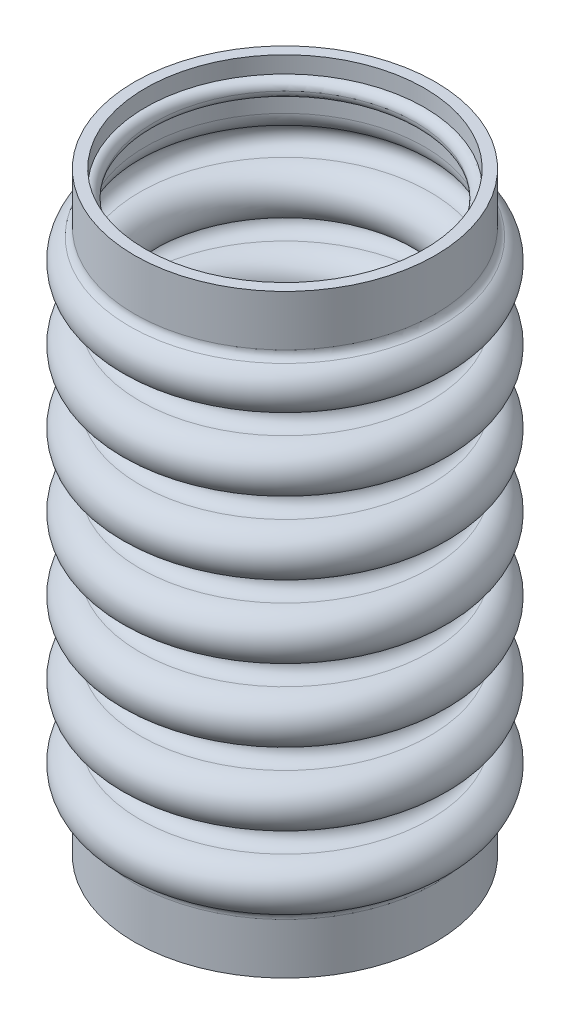
SolidWorks part; units mm, degrees
ref_plane "Front Plane" through (0, 0, 0) normal (0, 0, 1) x (1, 0, 0)
ref_plane "Top Plane" through (0, 0, 0) normal (0, 1, 0) x (1, 0, 0)
ref_plane "Right Plane" through (0, 0, 0) normal (1, 0, 0) x (0, 0, -1)
sketch "Sketch1" plane through (0, 0, 0) normal (0, 0, 1) x (1, 0, 0)
  line L0 (-46.087, 0) -> (53.9921, 0) construction
  line L1 (0, 81.831) -> (0, -42.6877) construction
  line L2 (-20, 0) -> (-20, 8.4666) construction
  line L3 (-20, 5) -> (0, 5) construction
  line L4 (0, 80) -> (-20, 80) construction
  line L5 (-20, 85) -> (-20, 76.5349) construction
  line L6 (-20.75, 85) -> (-20.75, 76.5349)
  line L7 (-20.75, 0) -> (-20.75, 8.4666)
  line L8 (-19.25, 85) -> (-19.25, 76.5349)
  line L9 (-19.25, 0) -> (-19.25, 8.4666)
  line L10 (-20.75, 85) -> (-19.25, 85)
  line L11 (-20.75, 0) -> (-19.25, 0)
  arc A0 (-21.1132, 10.2592) -> (-20.0029, 15) centre (-20.0046, 12.5) cw construction
  arc A1 (-20.0029, 15) -> (-20.0044, 20) centre (-20.0012, 17.5) ccw construction
  arc A2 (-20.0044, 20) -> (-20.0029, 25) centre (-20.0046, 22.5) cw construction
  arc A3 (-20.0029, 25) -> (-20.0044, 30) centre (-20.0012, 27.5) ccw construction
  arc A4 (-20.0044, 30) -> (-20.0029, 35) centre (-20.0046, 32.5) cw construction
  arc A5 (-20.0029, 35) -> (-20.0044, 40) centre (-20.0012, 37.5) ccw construction
  arc A6 (-20.0044, 40) -> (-20.0029, 45) centre (-20.0046, 42.5) cw construction
  arc A7 (-20.0029, 45) -> (-20.0044, 50) centre (-20.0012, 47.5) ccw construction
  arc A8 (-20.0044, 50) -> (-20.0029, 55) centre (-20.0046, 52.5) cw construction
  arc A9 (-20.0029, 55) -> (-20.0044, 60) centre (-20.0012, 57.5) ccw construction
  arc A10 (-20.0044, 60) -> (-20.0029, 65) centre (-20.0046, 62.5) cw construction
  arc A11 (-20.0029, 65) -> (-20.0044, 70) centre (-20.0012, 67.5) ccw construction
  arc A12 (-20.0044, 70) -> (-21.1145, 74.7416) centre (-20.0076, 72.5) cw construction
  arc A13 (-20, 76.5349) -> (-21.1145, 74.7416) centre (-22, 76.5349) cw construction
  arc A14 (-21.1132, 10.2592) -> (-20, 8.4666) centre (-22, 8.4666) cw construction
  arc A15 (-20.75, 76.5349) -> (-21.4465, 75.4141) centre (-22, 76.5349) cw
  arc A16 (-20.0034, 69.25) -> (-21.4465, 75.4141) centre (-20.0076, 72.5) cw
  arc A17 (-20.0024, 65.75) -> (-20.0034, 69.25) centre (-20.0012, 67.5) ccw
  arc A18 (-20.0039, 59.25) -> (-20.0024, 65.75) centre (-20.0046, 62.5) cw
  arc A19 (-20.0024, 55.75) -> (-20.0039, 59.25) centre (-20.0012, 57.5) ccw
  arc A20 (-20.0039, 49.25) -> (-20.0024, 55.75) centre (-20.0046, 52.5) cw
  arc A21 (-20.0024, 45.75) -> (-20.0039, 49.25) centre (-20.0012, 47.5) ccw
  arc A22 (-20.0039, 39.25) -> (-20.0024, 45.75) centre (-20.0046, 42.5) cw
  arc A23 (-20.0024, 35.75) -> (-20.0039, 39.25) centre (-20.0012, 37.5) ccw
  arc A24 (-20.0039, 29.25) -> (-20.0024, 35.75) centre (-20.0046, 32.5) cw
  arc A25 (-20.0024, 25.75) -> (-20.0039, 29.25) centre (-20.0012, 27.5) ccw
  arc A26 (-20.0039, 19.25) -> (-20.0024, 25.75) centre (-20.0046, 22.5) cw
  arc A27 (-20.0024, 15.75) -> (-20.0039, 19.25) centre (-20.0012, 17.5) ccw
  arc A28 (-21.4457, 9.587) -> (-20.0024, 15.75) centre (-20.0046, 12.5) cw
  arc A29 (-21.4457, 9.587) -> (-20.75, 8.4666) centre (-22, 8.4666) cw
  arc A30 (-19.25, 76.5349) -> (-20.7824, 74.0691) centre (-22, 76.5349) cw
  arc A31 (-20.0053, 70.75) -> (-20.7824, 74.0691) centre (-20.0076, 72.5) cw
  arc A32 (-20.0034, 64.25) -> (-20.0053, 70.75) centre (-20.0012, 67.5) ccw
  arc A33 (-20.0049, 60.75) -> (-20.0034, 64.25) centre (-20.0046, 62.5) cw
  arc A34 (-20.0034, 54.25) -> (-20.0049, 60.75) centre (-20.0012, 57.5) ccw
  arc A35 (-20.0049, 50.75) -> (-20.0034, 54.25) centre (-20.0046, 52.5) cw
  arc A36 (-20.0034, 44.25) -> (-20.0049, 50.75) centre (-20.0012, 47.5) ccw
  arc A37 (-20.0049, 40.75) -> (-20.0034, 44.25) centre (-20.0046, 42.5) cw
  arc A38 (-20.0034, 34.25) -> (-20.0049, 40.75) centre (-20.0012, 37.5) ccw
  arc A39 (-20.0049, 30.75) -> (-20.0034, 34.25) centre (-20.0046, 32.5) cw
  arc A40 (-20.0034, 24.25) -> (-20.0049, 30.75) centre (-20.0012, 27.5) ccw
  arc A41 (-20.0049, 20.75) -> (-20.0034, 24.25) centre (-20.0046, 22.5) cw
  arc A42 (-20.0034, 14.25) -> (-20.0049, 20.75) centre (-20.0012, 17.5) ccw
  arc A43 (-20.7806, 10.9314) -> (-20.0034, 14.25) centre (-20.0046, 12.5) cw
  arc A44 (-20.7806, 10.9314) -> (-19.25, 8.4666) centre (-22, 8.4666) cw
  point P45 (-20, 75)
  point P48 (-20, 10)
  point P49 (-20, 75)
  dimension "D3" = 2.5
  dimension "D4" = 2.5
  dimension "D12" = 2
  dimension "D13" = 2
  dimension "D1" = 20
  dimension "D2" = 10
  dimension "D5" = 5
  dimension "D6" = 75
  dimension "D7" = 10
  dimension "D8" = 5
  dimension "D10" = 20
  dimension "D11" = 5
  dimension "D14" = 0.75
  dimension "D15" = 0.75
  dimension "D9" = 6
revolve "Revolve1" add sketch "Sketch1" angle 360 about L1
sketch "Sketch3" plane through (0, 0, 0) normal (1, 0, 0) x (0, 0, -1)
  line L0 (20.75, 76.5349) -> (20.75, 85) construction
  line L1 (-20.75, 85) -> (20.75, 85)
  line L2 (-20.75, 85) -> (-20.75, 83.5349)
  line L3 (-20.75, 83.5349) -> (20.75, 83.5349)
  line L4 (20.75, 85) -> (20.75, 83.5349)
  line L5 (20.75, 0) -> (20.75, 8.4666) construction
  line L6 (-20.75, 0) -> (20.75, 0)
  line L7 (-20.75, 0) -> (-20.75, 1.4666)
  line L8 (-20.75, 1.4666) -> (20.75, 1.4666)
  line L9 (20.75, 0) -> (20.75, 1.4666)
  line L10 (-20.75, 8.4666) -> (20.75, 8.4666) construction
  line L11 (-20.75, 76.5349) -> (20.75, 76.5349) construction
  dimension "D2" = 7
  dimension "D1" = 7
extrude "Cut-Extrude1" cut sketch "Sketch3" against normal through all both and the other way through all
ref_plane "Plane3" through (0, 42.5007, 0) normal (0, 1, 0) x (1, 0, 0)
ref_plane "Plane4" through (0, 80.0349, 0) normal (0, 1, 0) x (1, 0, 0)
sketch "Sketch4" plane through (0, 80.0349, 0) normal (0, 1, 0) x (1, 0, 0)
  circle A0 centre (0, 0) radius 19.25 construction
  circle A1 centre (0, 0) radius 19.25
  circle A2 centre (0, 0) radius 18.05
  dimension "D1" = 1.2
extrude "Boss-Extrude2" add sketch "Sketch4" along normal mid plane 2.4
fillet "Fillet2" radius 1.2 2 edges at (0, 78.8349, 18.05) (0, 81.2349, 18.05)
mirror "Mirror3" about plane through (0, 42.5007, 0) normal (0, 1, 0) of "Boss-Extrude2", "Fillet2"
equation "\"D1@Sketch3\"=\"D2@Sketch3\""
